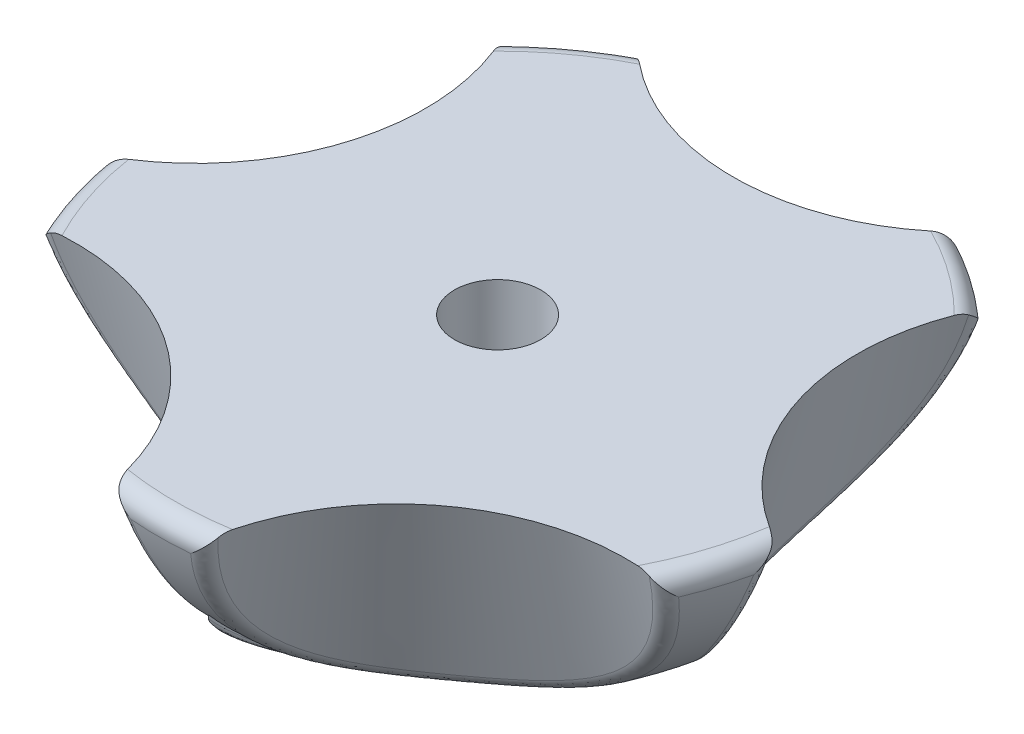
SolidWorks part; units mm, degrees
ref_plane "Plan de face" through (0, 0, 0) normal (0, 0, 1) x (1, 0, 0)
ref_plane "Plan de dessus" through (0, 0, 0) normal (0, 1, 0) x (1, 0, 0)
ref_plane "Plan de droite" through (0, 0, 0) normal (1, 0, 0) x (0, 0, -1)
sketch "Esquisse1" plane through (0, 0, 0) normal (0, 1, 0) x (1, 0, 0)
  circle A0 centre (0, 0) radius 2.5
  circle A1 centre (0, 0) radius 20
  dimension "D1" = 5
  dimension "D2" = 40
extrude "Boss.-Extru.1" add sketch "Esquisse1" along normal blind 12
fillet "Congé7" radius 15 1 edges at (0, 0, 20)
sketch "Esquisse2" plane through (0, 12, 0) normal (0, 1, 0) x (1, 0, 0)
  line L0 (0, 0) -> (0, 17.1605) construction
  arc A0 (-9.4826, 17.6091) -> (9.3573, 17.676) centre (-0.0961, 27.0625) ccw
  arc A2 (-9.4826, 17.6091) -> (9.3573, 17.676) centre (0, 0) cw
  dimension "D2" = 18.84
extrude "Enlèv. mat.-Extru.1" cut sketch "Esquisse2" against normal through all draft 15 draft outward yes
ref_axis "Axe1" through (0, -0.4, 0) along (0, 1, 0)
pattern_circular "Répétition circulaire1" count 5 over 360 about axis through (0, -0.4, 0) along (0, 1, 0) of "Enlèv. mat.-Extru.1"
sketch "Esquisse3" plane through (0, 0, 0) normal (0, -1, 0) x (1, 0, 0)
  circle A1 centre (0, 0) radius 5.3031
  circle A2 centre (0, 0) radius 5.3031
  dimension "D1" = 0
extrude "Enlèv. mat.-Extru.2" cut sketch "Esquisse3" against normal blind 2 draft 45
fillet "Congé9" radius 1 11 edges at (0, 0, -5.3031) (-18.9991, 12, 6.2478) (-7.0525, 1.0722, 8.2745) (0.071, 12, 19.9999) (5.6902, 1.0722, 9.2643) (19.0429, 12, 6.1128) (10.5693, 1.0722, -2.5489) (11.6982, 12, -16.222) (0.842, 1.0722, -10.8396) (-11.8131, 12, -16.1385) (-10.0489, 1.0722, -4.1504)
sketch "Esquisse4" plane through (0, 0, 0) normal (0, 1, 0) x (1, 0, 0)
  line L0 (0, -16.7711) -> (0, 0) construction
  line L1 (-1.8903, -11.1291) -> (1.8903, -11.1291)
  spline S0 degree 3 poles (0, -16.7711) (-0.3951, -14.5086) (-0.1884, -13.6813) (-1.8903, -11.1291) knots 0 0 0 0 1 1 1 1
  spline S2 degree 3 poles (0, -16.7711) (0.3951, -14.5086) (0.1884, -13.6813) (1.8903, -11.1291) knots 0 0 0 0 1 1 1 1
extrude "Boss.-Extru.2" add sketch "Esquisse4" along normal up to next contours S2 L1 S0
sketch "Esquisse5" plane through (0, 0, 0) normal (1, 0, 0) x (0, 0, -1)
  line L0 (0, -0.4) -> (0, 8.4) construction
  line L1 (-11.1291, 1.2459) -> (-11.1291, 0) construction
  line L2 (0, -7.6554) -> (-24.1202, -7.6554)
  line L3 (-20.3663, 12.752) -> (-20.3663, 11.4362)
  line L4 (-24.1202, -7.6554) -> (-24.1202, 12.752)
  line L5 (-24.1202, 12.752) -> (-20.3663, 12.752)
  line L6 (-11.1291, 0.9251) -> (0, -7.6554)
  line L7 (0, 0) -> (0, -7.6554) construction
  arc A0 (-20.3663, 11.4362) -> (-11.1291, 0.9251) centre (-5.1247, 15.5161) ccw
extrude "Enlèv. mat.-Extru.4" cut sketch "Esquisse5" against normal mid plane 5
fillet "Congé10" radius 0.2 3 edges at (0.2614, 3.2378, 15.0339) (0, 0.9251, 11.1291) (-0.2614, 3.2378, 15.0339)
